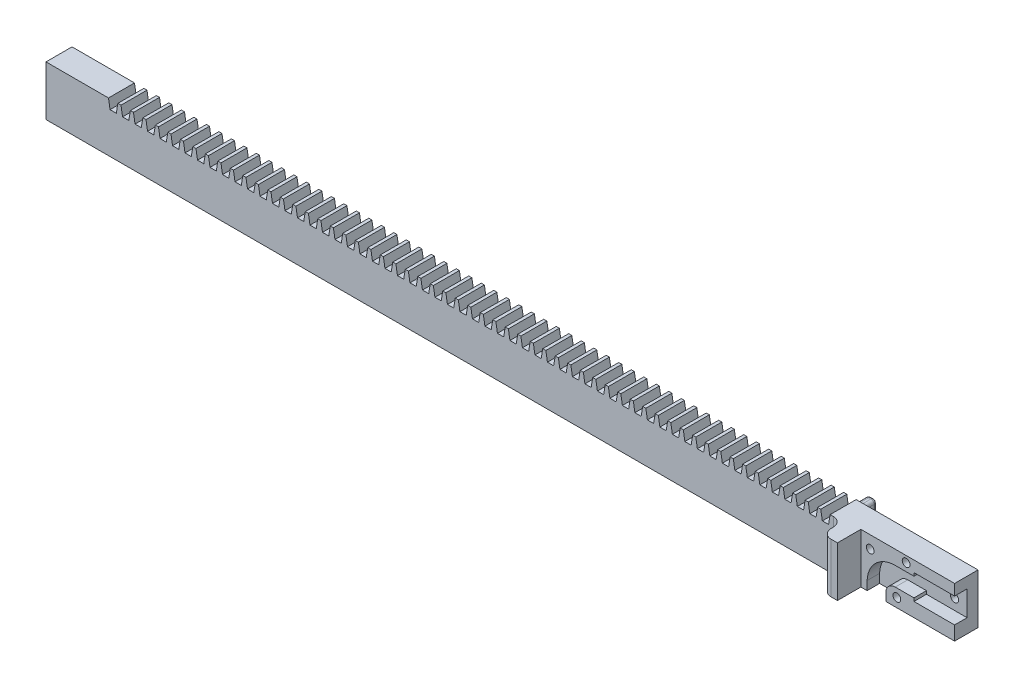
SolidWorks part; units mm, degrees
ref_plane "Front Plane" through (0, 0, 0) normal (0, 0, 1) x (1, 0, 0)
ref_plane "Top Plane" through (0, 0, 0) normal (0, 1, 0) x (1, 0, 0)
ref_plane "Right Plane" through (0, 0, 0) normal (1, 0, 0) x (0, 0, -1)
sketch "Sketch1" plane through (0, 0, 0) normal (1, 0, 0) x (0, 0, -1)
  line L1 (7.5, -8) -> (7.5, 8)
  line L2 (7.5, 8) -> (-7.5, 8)
  line L3 (-7.5, 8) -> (-7.5, -8)
  line L4 (-7.5, 8) -> (7.5, -8) construction
  line L5 (7.5, 8) -> (-7.5, -8) construction
  line L6 (0, 8) -> (0, -8) construction
  line L10 (2, -6) -> (1.5, -8)
  line L11 (4, -6) -> (2, -6)
  line L12 (4.5, -8) -> (4, -6)
  line L13 (0, -8) -> (1.5, -8)
  line L14 (4.5, -8) -> (7.5, -8)
  line L16 (-7.5, -8) -> (0, -8)
  point P2 (0, 0)
  dimension "D1" = 15
  dimension "D2" = 16
  dimension "D3" = 3
  dimension "D4" = 2
  dimension "D5" = 2
  dimension "D6" = 3
  dimension "D7" = 3.5
  dimension "D8" = 7.5
  dimension "D9" = 1.5
extrude "Boss-Extrude1" add sketch "Sketch1" along normal blind 120 and the other way blind 140
sketch "Sketch2" plane through (0, 0, 7.5) normal (0, 0, 1) x (1, 0, 0)
  line L0 (-120, 17) -> (-120, -8) construction
  line L1 (110, 17) -> (110, -8) construction
  line L2 (-140, 8) -> (-140, -8) construction
  line L4 (-140, -8) -> (120, -8) construction
  point P6 (-140, 0)
  dimension "D1" = 20
  dimension "D2" = 230
  dimension "D3" = 25
sketch "Sketch3" plane through (0, 0, 7.5) normal (0, 0, 1) x (1, 0, 0)
  line L0 (-120, 8) -> (-119.5, 5)
  line L1 (-119.5, 5) -> (-117.5, 5)
  line L2 (-117.5, 5) -> (-117, 8)
  line L3 (-140, 8) -> (120, 8) construction
  line L4 (-120, 17) -> (-120, -8) construction
  line L5 (-120, 8) -> (-117, 8)
  dimension "D1" = 2
  dimension "D2" = 3
  dimension "D3" = 3
  dimension "D4" = 0.5
extrude "Cut-Extrude1" cut sketch "Sketch3" against normal up to next
pattern_linear "LPattern1" count 58 spacing 4 along (1, 0, 0) of "Cut-Extrude1"
sketch "Sketch5" plane through (120, 0, 0) normal (1, 0, 0) x (0, 0, -1)
  line L0 (7.5, 8) -> (-7.5, 8) construction
  line L1 (7.5, -8) -> (7.5, 8) construction
  line L2 (-7.5, 8) -> (-7.5, -8) construction
  line L3 (7.5, 8) -> (-7.5, 8)
  line L4 (7.5, -8) -> (7.5, 8)
  line L5 (-7.5, 8) -> (-7.5, -8)
  line L6 (-7.5, -8) -> (7.5, -8)
  line L7 (0, 8) -> (0, -8)
  line M11 (1.5, -8) -> (2, -6)
  line M12 (2, -6) -> (4, -6)
  line M13 (4, -6) -> (4.5, -8)
  line M14 (4.5, -8) -> (7.5, -8)
  line M15 (7.5, -8) -> (7.5, 8)
  line M16 (7.5, 8) -> (-7.5, 8)
extrude "Boss-Extrude2" add sketch "Sketch5" along normal blind 30 contours L7 L6 M16 M11 M12 M13 M14 M15 | L6 M11 M13 M12 region at (120, 0.3072, -3.7826) region at (120, -7.0667, -3)
sketch "Sketch6" plane through (0, 0, 0) normal (0, 0, 1) x (1, 0, 0)
  line L1 (150, -3.5) -> (137, -3.5)
  line L2 (137, -3.5) -> (137, -2.5)
  line L3 (137, -2.5) -> (131, -2.5)
  line L4 (128.005, -5.2) -> (128.005, -8)
  line L5 (128.005, -8) -> (122.005, -8)
  line L6 (122.005, -8) -> (122.005, -5.2)
  line L7 (131, 3.5) -> (137, 3.5)
  line L8 (137, 3.5) -> (137, 4.5)
  line L9 (137, 4.5) -> (150, 4.5)
  line L11 (150, 4.5) -> (150, -3.5)
  line L12 (150, 8) -> (150, -8) construction
  line L14 (150, -8) -> (120, -8) construction
  arc A0 (131, -2.5) -> (128.005, -5.2) centre (130.99, -5.5) ccw
  arc A1 (122.005, -5.2) -> (131, 3.5) centre (131, -5.5) cw
  point P16 (128.9359, -2.5)
  dimension "D4" = 3
  dimension "D5" = 9
  dimension "D9" = 6
  dimension "D1" = 13
  dimension "D2" = 8
  dimension "D3" = 6
  dimension "D6" = 6
  dimension "D7" = 4.5
  dimension "D8" = 2.8
extrude "Cut-Extrude2" cut sketch "Sketch6" against normal blind 4
sketch "Sketch7" plane through (0, 0, 0) normal (0, 0, 1) x (1, 0, 0)
  line L0 (150, 8) -> (120, 8) construction
  line L1 (120, 8) -> (120, -8) construction
  line L2 (131, -2.5) -> (137, -2.5) construction
  line L3 (128.005, -8) -> (128.005, -5.2) construction
  line L4 (137, 4.5) -> (137, 3.5) construction
  point P0 (123, 4)
  point P2 (134.5, 6)
  point P3 (131.505, -5.1)
  point P13 (0, 0)
  dimension "D1" = 4
  dimension "D2" = 3
  dimension "D3" = 2.6
  dimension "D4" = 3.5
  dimension "D5" = 2
  dimension "D6" = 2.5
hole_wizard "M3 Tapped Hole1" positions "Sketch8" profile "Sketch9" tap size "M3" standard "ISO" end condition up to next
sketch "Sketch8" plane through (0, 0, 0) normal (0, 0, 1) x (1, 0, 0)
  point P0 (134.5, 6)
  point P3 (131.505, -5.1)
  point P6 (123, 4)
sketch "Sketch9" plane through (134.5, 6, 0) normal (1, 0, 0) x (0, -1, 0)
  line L0 (0, 0) -> (0, 7.5)
  line L1 (0, 7.5) -> (1.25, 7.5)
  line L2 (1.25, 7.5) -> (1.25, 0)
  line L5 (1.25, 0) -> (0, 0)
  line L11 (0, -6.35) -> (0, 107.95) construction
  dimension "Thru Tap Drill Dia." = 2.5
  dimension "Thru Tap Drill Depth" = 7.5
cosmetic thread "Hole Thread1" parameters "D2"=3
cosmetic thread "Hole Thread2" parameters "D2"=3
cosmetic thread "Hole Thread3" parameters "D2"=3
ref_plane "Plane3" through (0, 0, 0) normal (0, 0, 1) x (1, 0, 0)
sketch "Sketch11" plane through (-140, 0, 0) normal (-1, 0, 0) x (0, 0, 1)
  line L0 (0.83, 10.0046) -> (9.9775, -11.119) construction
  line L1 (0.83, 10.0046) -> (9.9775, 10.0046)
  line L2 (0.83, 10.0046) -> (0.83, -11.119)
  line L3 (0.83, -11.119) -> (9.9775, -11.119)
  line L4 (9.9775, 10.0046) -> (9.9775, -11.119)
  line L5 (9.9775, 10.0046) -> (0.83, -11.119) construction
  dimension "D1" = 9.1474
  dimension "D2" = 21.1236
  dimension "D3" = 0.83
  dimension "D4" = 11.119
extrude "Cut-Extrude4" cut sketch "Sketch11" against normal blind 255
sketch "Sketch12" plane through (0, 0, -7.5) normal (0, 0, -1) x (-1, 0, 0)
  line L0 (-150, -8) -> (-150, 8) construction
  line L1 (-111, 8) -> (-150, 8) construction
  circle A0 centre (-146, 0) radius 1.3
  dimension "D1" = 2.6
  dimension "D2" = 4
  dimension "D3" = 8
extrude "Cut-Extrude5" cut sketch "Sketch12" against normal up to next
sketch "Sketch14" plane through (-140, 0, 0) normal (-1, 0, 0) x (0, 0, 1)
  line L0 (-7.5, 1.5) -> (-5.5, 1)
  line L1 (-5.5, 1) -> (-5.5, -1)
  line L2 (-5.5, -1) -> (-7.5, -1.5)
  line L3 (-7.5, -8) -> (-7.5, 8) construction
  line L4 (-7.5, 8) -> (7.5, 8) construction
  line L5 (-7.5, 1.5) -> (-7.5, -1.5)
  dimension "D1" = 2
  dimension "D2" = 2
  dimension "D3" = 3
  dimension "D4" = 6.5
  dimension "D5" = 7
extrude "Cut-Extrude6" cut sketch "Sketch14" against normal blind 248
fillet "Fillet1" radius 3 2 edges at (115, 0, 7.5) (115, 0, 0.83)
sketch "Sketch16" plane through (0, 0, -7.5) normal (0, 0, -1) x (-1, 0, 0)
  line L0 (-108, 1.5) -> (-108, -1.5) construction
  line L1 (-110.7, 4.5) -> (-108, 4.5)
  line L2 (-110.7, 4.5) -> (-110.7, -7.5)
  line L3 (-110.7, -7.5) -> (-108, -7.5)
  line L4 (-108, 4.5) -> (-108, -7.5)
  line L7 (140, -8) -> (-150, -8) construction
  dimension "D1" = 12
  dimension "D2" = 2.7
  dimension "D3" = 0.5
extrude "Boss-Extrude3" add sketch "Sketch16" along normal blind 7
fillet "Fillet2" radius 3 1 edges at (110.7, -1.5, -7.5)
fillet "Fillet3" radius 1 10 edges at (109.35, -7.5, -14.5) (109.35, 4.5, -14.5) (108, -1.5, -14.5) (110.7, -1.5, -14.5) (111.5787, 4.5, -8.3787) (111.5787, -7.5, -8.3787) (108, 4.5, -11) (110.7, 4.5, -12.5) (108, -7.5, -11) (110.7, -7.5, -12.5)
